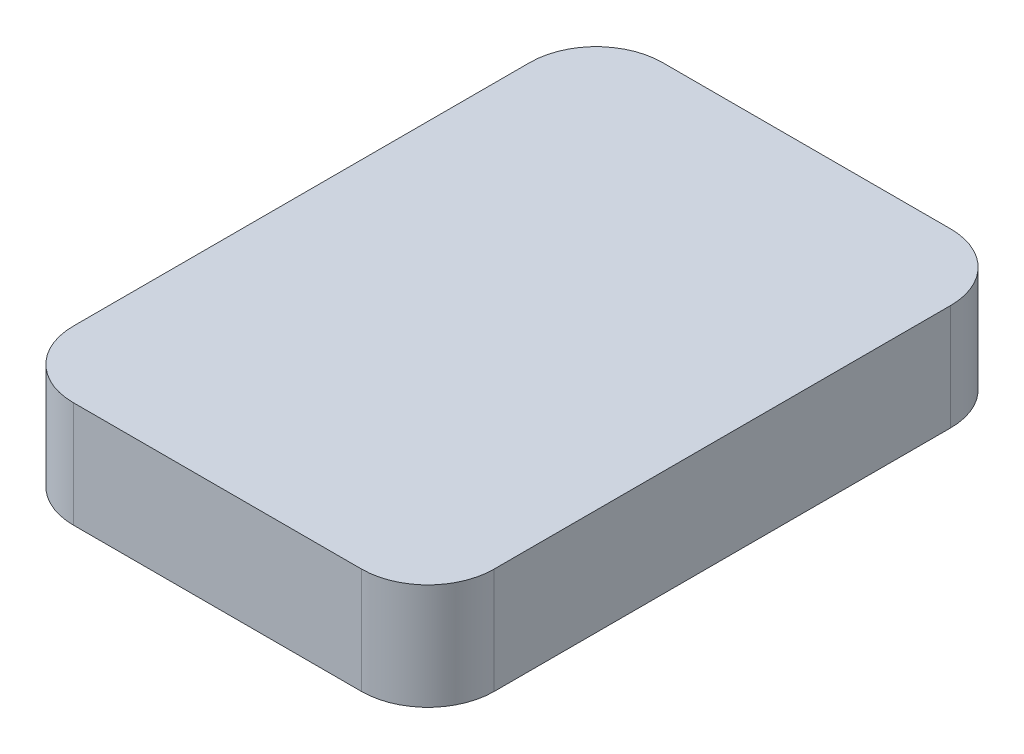
SolidWorks part; units mm, degrees
ref_plane "Front Plane" through (0, 0, 0) normal (0, 0, 1) x (1, 0, 0)
ref_plane "Top Plane" through (0, 0, 0) normal (0, 1, 0) x (1, 0, 0)
ref_plane "Right Plane" through (0, 0, 0) normal (1, 0, 0) x (0, 0, -1)
sketch "Sketch1" plane through (0, 0, 0) normal (0, 1, 0) x (1, 0, 0)
  line L1 (-31.75, -44.45) -> (31.75, -44.45)
  line L2 (-31.75, -44.45) -> (-31.75, 44.45)
  line L3 (-31.75, 44.45) -> (31.75, 44.45)
  line L4 (31.75, -44.45) -> (31.75, 44.45)
  line L5 (-31.75, -44.45) -> (31.75, 44.45) construction
  line L6 (-31.75, 44.45) -> (31.75, -44.45) construction
  point P0 (0, 0)
  dimension "D1" = 63.5
  dimension "D2" = 88.9
extrude "Boss-Extrude1" add sketch "Sketch1" along normal blind 16
fillet "Fillet1" radius 10 4 edges at (31.75, 8, 44.45) (31.75, 8, -44.45) (-31.75, 8, -44.45) (-31.75, 8, 44.45)
